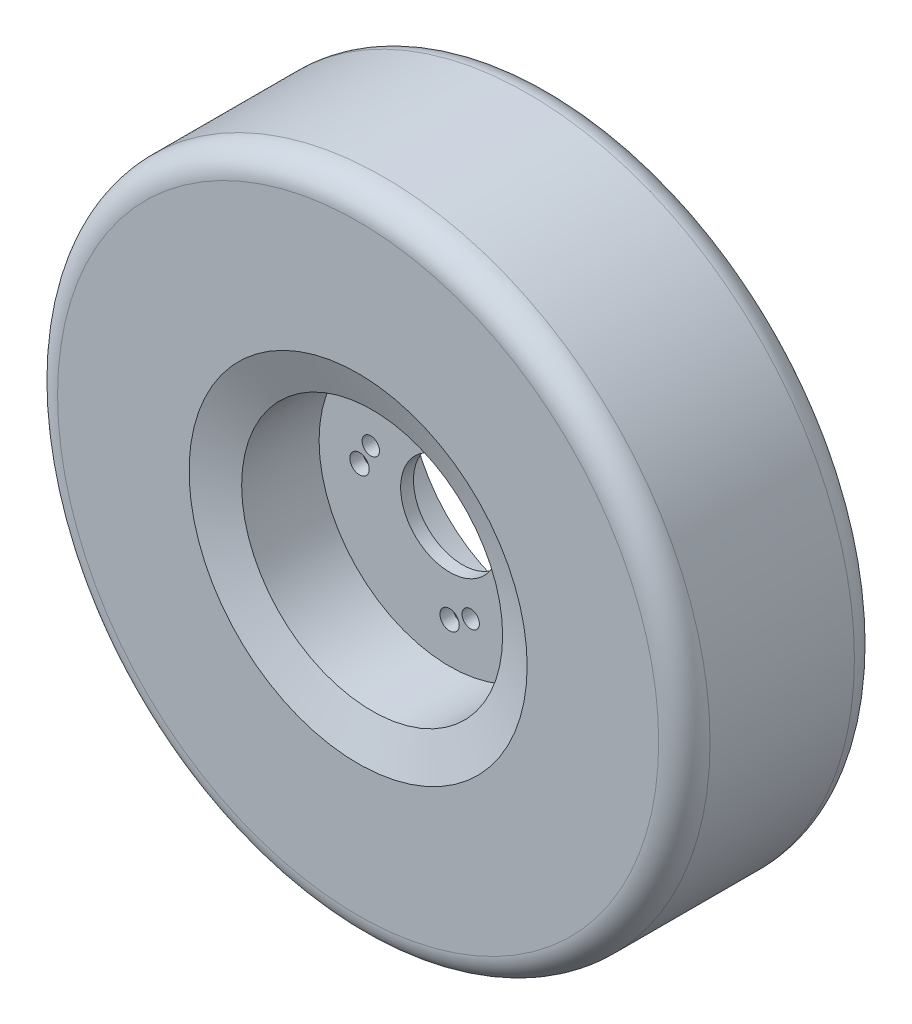
SolidWorks part; units mm, degrees
ref_plane "Front Plane" through (0, 0, 0) normal (0, 0, 1) x (1, 0, 0)
ref_plane "Top Plane" through (0, 0, 0) normal (0, 1, 0) x (1, 0, 0)
ref_plane "Right Plane" through (0, 0, 0) normal (1, 0, 0) x (0, 0, -1)
sketch "Sketch1" plane through (0, 0, 0) normal (0, 0, 1) x (1, 0, 0)
  circle A0 centre (0, 0) radius 50.8
  circle A1 centre (0, 0) radius 127
  dimension "D1" = 254
  dimension "D2" = 101.6
extrude "Boss-Extrude1" add sketch "Sketch1" along normal mid plane 76.2
chamfer "Chamfer1" distance 15 angle 20 2 edges at (50.8, 0, 38.1) (50.8, 0, -38.1) first distance on face at (127, 0, 38.1) first distance on face at (127, 0, -38.1)
fillet "Fillet1" radius 10 2 edges at (127, 0, -38.1) (127, 0, 38.1)
sketch "Sketch2" plane through (0, 0, 0) normal (0, 0, 1) x (1, 0, 0)
  circle A0 centre (0, 0) radius 50.8
  circle A1 centre (0, 0) radius 50.8 construction
  circle A2 centre (0, 0) radius 19.05
  dimension "D1" = 38.1
extrude "Boss-Extrude2" add sketch "Sketch2" along normal mid plane 5
hole_wizard "19/64 (0.29688) Diameter Hole1" positions "Sketch3" profile "Sketch4" hole size "19/64" standard "ANSI Inch"
sketch "Sketch3" plane through (0, 0, 2.5) normal (0, 0, 1) x (1, 0, 0)
  line L0 (0, -35.052) -> (0, 0) construction
  line L1 (0, 0) -> (35.052, 0) construction
  line L3 (0, 35.052) -> (0, 0) construction
  line L4 (0, 0) -> (-35.052, 0) construction
  circle A0 centre (0, 0) radius 35.052 construction
  point P0 (0, 35.052)
  point P2 (35.052, 0)
  point P4 (0, -35.052)
  point P6 (-35.052, 0)
  point P29 (8.1816, -27.9129)
  dimension "D1" = 70.104
sketch "Sketch4" plane through (0, 35.052, 2.5) normal (1, 0, 0) x (0, -1, 0)
  line L0 (0, 0) -> (0, 21.0155)
  line L1 (0, 21.0155) -> (3.7704, 18.75)
  line L2 (3.7704, 18.75) -> (3.7704, 0)
  line L5 (3.7704, 0) -> (0, 0)
  line L10 (0, 21.0155) -> (-3.7704, 18.75) construction
  line L11 (0, -6.35) -> (0, 107.95) construction
  dimension "Hole Dia." = 7.5408
  dimension "Hole Depth" = 18.75
  dimension "Drill Angle" = 118
hole_wizard "1/4 Clearance Hole1" positions "Sketch7" profile "Sketch8" hole size "1/4" standard "ANSI Inch"
sketch "Sketch7" plane through (0, 0, 2.5) normal (0, 0, 1) x (1, 0, 0)
  line L0 (-30.6681, 8.2175) -> (0, 0) construction
  line L1 (0, 0) -> (8.2175, -30.6681) construction
  line L4 (0, 0) -> (22.4506, 22.4506) construction
  line L6 (-35.052, 0) -> (35.052, 0) construction
  line L8 (0, 0) -> (-22.4506, -22.4506) construction
  circle A0 centre (0, 0) radius 31.75 construction
  point P0 (-30.6681, 8.2175)
  point P2 (22.4506, 22.4506)
  point P4 (8.2175, -30.6681)
  point P40 (0, 0)
  dimension "D3" = 63.5
  dimension "D1" = 120
  dimension "D2" = 120
  dimension "D4" = 45
  dimension "D5" = 60
sketch "Sketch8" plane through (-30.6681, 8.2175, 2.5) normal (1, 0, 0) x (0, -1, 0)
  line L0 (0, 0) -> (0, 20.7798)
  line L1 (0, 20.7798) -> (3.3782, 18.75)
  line L2 (3.3782, 18.75) -> (3.3782, 0)
  line L5 (3.3782, 0) -> (0, 0)
  line L10 (0, 20.7798) -> (-3.3782, 18.75) construction
  line L11 (0, -6.35) -> (0, 107.95) construction
  dimension "Hole Dia." = 6.7564
  dimension "Hole Depth" = 18.75
  dimension "Drill Angle" = 118
